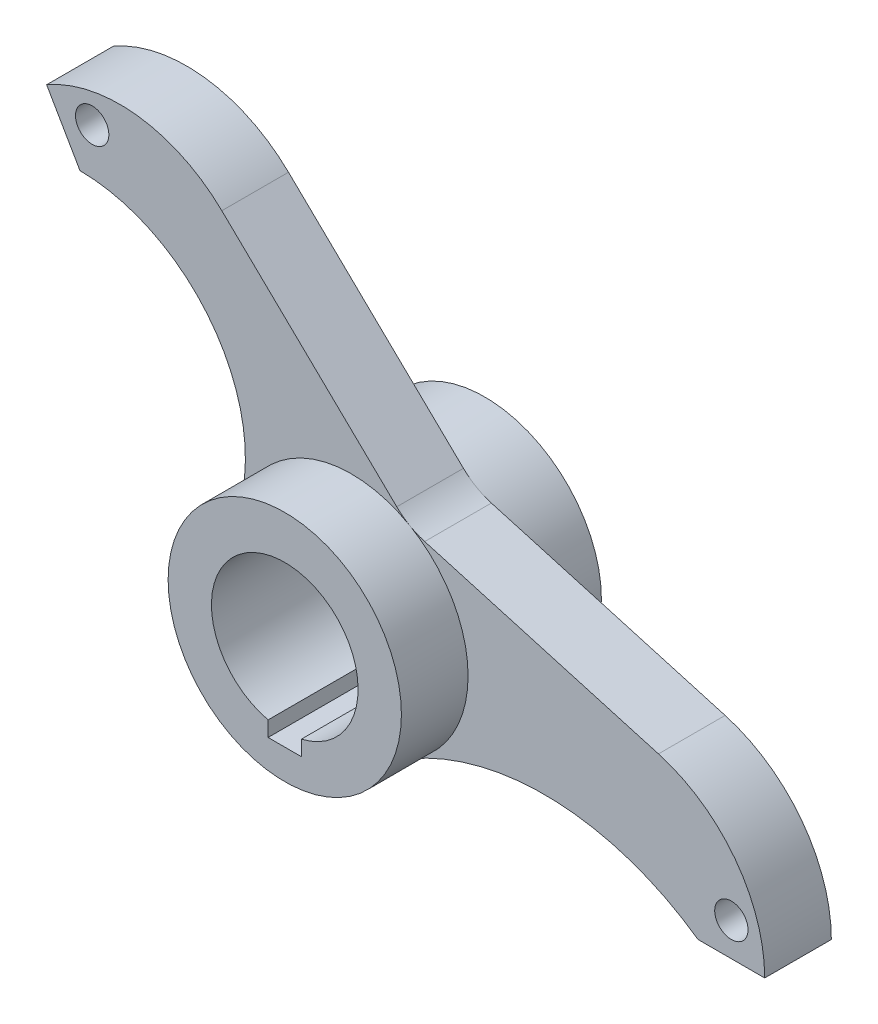
SolidWorks part; units mm, degrees
ref_plane "Piano frontale" through (0, 0, 0) normal (0, 0, 1) x (1, 0, 0)
ref_plane "Piano superiore" through (0, 0, 0) normal (0, 1, 0) x (1, 0, 0)
ref_plane "Piano destro" through (0, 0, 0) normal (1, 0, 0) x (0, 0, -1)
sketch "Schizzo1" plane through (0, 0, 0) normal (0, 0, 1) x (1, 0, 0)
  line L0 (0, 0) -> (57, 0) construction
  line L1 (0, 0) -> (-28.5, 49.3634) construction
  line L2 (-28.5, 49.3634) -> (-43.2224, 40.8634) construction
  line L3 (-45.7224, 45.1936) -> (-40.7224, 36.5333)
  line L4 (-45.5824, 54.9511) -> (-38.8923, 43.3634) construction
  line L5 (57, 0) -> (57, -17) construction
  line L6 (52, -17) -> (62, -17)
  line L7 (57, -12) -> (51.1127, -12) construction
  line L8 (-45.7224, 45.1936) -> (-20.9174, 59.5148) construction
  line L9 (-19.4396, 41.9661) -> (6.8032, 16.6225)
  line L10 (0, 0) -> (13.75, 23.8157) construction
  line L11 (62, -17) -> (62, 2.2699) construction
  line L12 (46.0635, 4.1479) -> (10.9939, 14.203)
  line L13 (0, 0) -> (0, -20.3704) construction
  line L14 (-2.5, -10.7121) -> (-2.5, -13)
  line L15 (-2.5, -13) -> (2.5, -13)
  line L16 (2.5, -10.7121) -> (2.5, -13)
  circle A0 centre (0, 0) radius 17.5
  arc A1 (-40.7224, 36.5333) -> (-16.8432, 4.7493) centre (-40.905, 11.534) cw
  arc A2 (-45.7224, 45.1936) -> (-19.4396, 41.9661) centre (-34.7224, 26.141) cw
  arc A3 (6.8032, 16.6225) -> (10.9939, 14.203) centre (13.75, 23.8157) ccw
  arc A4 (62, -17) -> (46.0635, 4.1479) centre (40, -17) ccw
  arc A5 (52, -17) -> (8.8084, -15.1216) centre (28.9419, -49.6852) ccw
  arc A6 (2.5, -10.7121) -> (-2.5, -10.7121) centre (0, 0) ccw
  point P9 (54.0564, -12)
  point P35 (0, -13)
  dimension "D10" = 35
  dimension "D11" = 25
  dimension "D12" = 22
  dimension "D14" = 10
  dimension "D15" = 22
  dimension "D16" = 40
  dimension "D19" = 11
  dimension "D1" = 60
  dimension "D2" = 57
  dimension "D3" = 17
  dimension "D4" = 10
  dimension "D5" = 5
  dimension "D6" = 10
  dimension "D7" = 5
  dimension "D8" = 17
  dimension "D9" = 57
  dimension "D13" = 60
  dimension "D17" = 5
  dimension "D18" = 13
extrude "Estrusione-Estrusione1" add sketch "Schizzo1" along normal mid plane 10 contours A3 L9 A2 L3 A1 A0 | A5 L6 A4 L12 A3 A0 region at (-20.1703, 31.6769, 0) region at (36.4809, -2.9836, 0)
extrude "Estrusione-Estrusione2" add sketch "Schizzo1<3>" along normal mid plane 30 contours A0 A6 L16 L15 L14 region at (-6.405, 15.7527, 0)
sketch "Schizzo1<3>" plane through (0, 0, 0) normal (0, 0, 1) x (1, 0, 0) same geometry as "Schizzo1"
hole_wizard "Foro Ø5.0 (5)-1" positions "Schizzo2" profile "Schizzo3" hole size "Ø5.0" standard "ISO" end condition up to next
sketch "Schizzo2" plane through (0, 0, 5) normal (0, 0, 1) x (1, 0, 0)
  point P0 (-38.8923, 43.3634)
  point P3 (57, -12)
sketch "Schizzo3" plane through (-38.8923, 43.3634, 5) normal (1, 0, 0) x (0, -1, 0)
  line L0 (0, 0) -> (0, 10)
  line L1 (0, 10) -> (2.5, 10)
  line L2 (2.5, 10) -> (2.5, 0)
  line L5 (2.5, 0) -> (0, 0)
  line L11 (0, -6.35) -> (0, 107.95) construction
  dimension "Thru Hole Dia." = 5
  dimension "Thru Hole Depth" = 10
